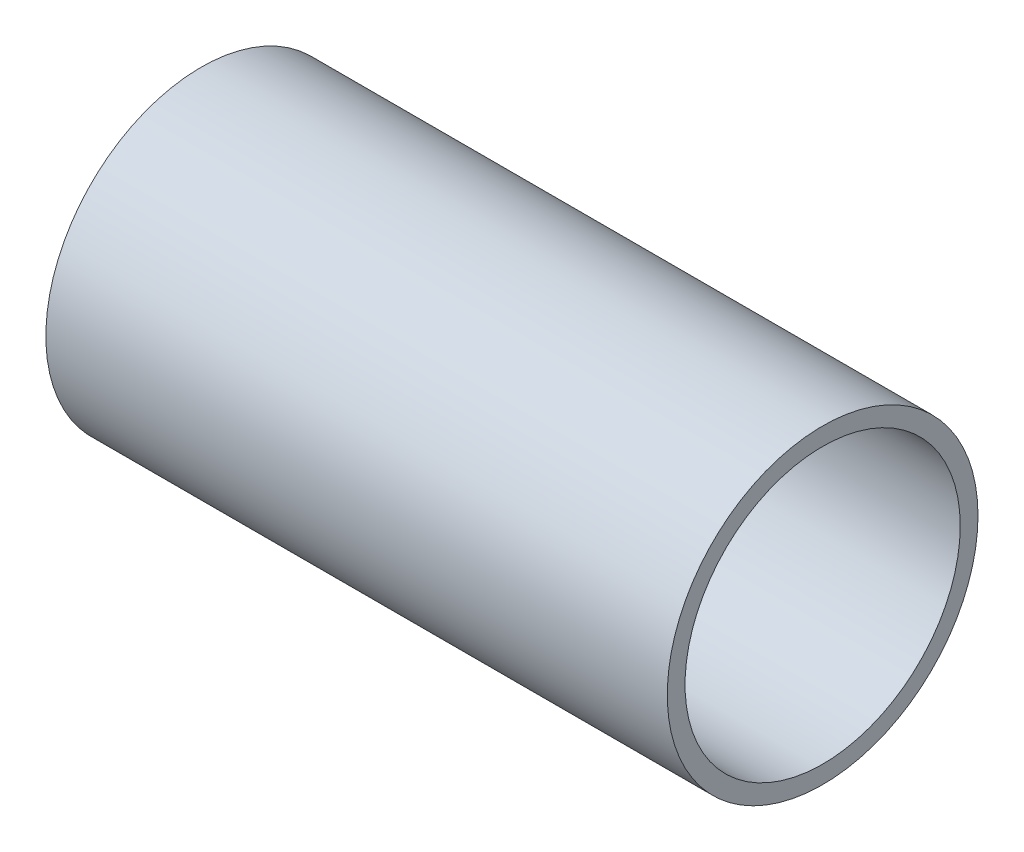
SolidWorks part; units mm, degrees
ref_plane "Спереди" through (0, 0, 0) normal (0, 0, 1) x (1, 0, 0)
ref_plane "Сверху" through (0, 0, 0) normal (0, 1, 0) x (1, 0, 0)
ref_plane "Справа" through (0, 0, 0) normal (1, 0, 0) x (0, 0, -1)
sketch "Эскиз1" plane through (0, 0, 0) normal (1, 0, 0) x (0, 0, -1)
  circle A0 centre (0, 0) radius 17.5
  circle A1 centre (0, 0) radius 15.5
  dimension "D1" = 35
  dimension "D2" = 31
extrude "Бобышка-Вытянуть1" add sketch "Эскиз1" along normal blind 70
